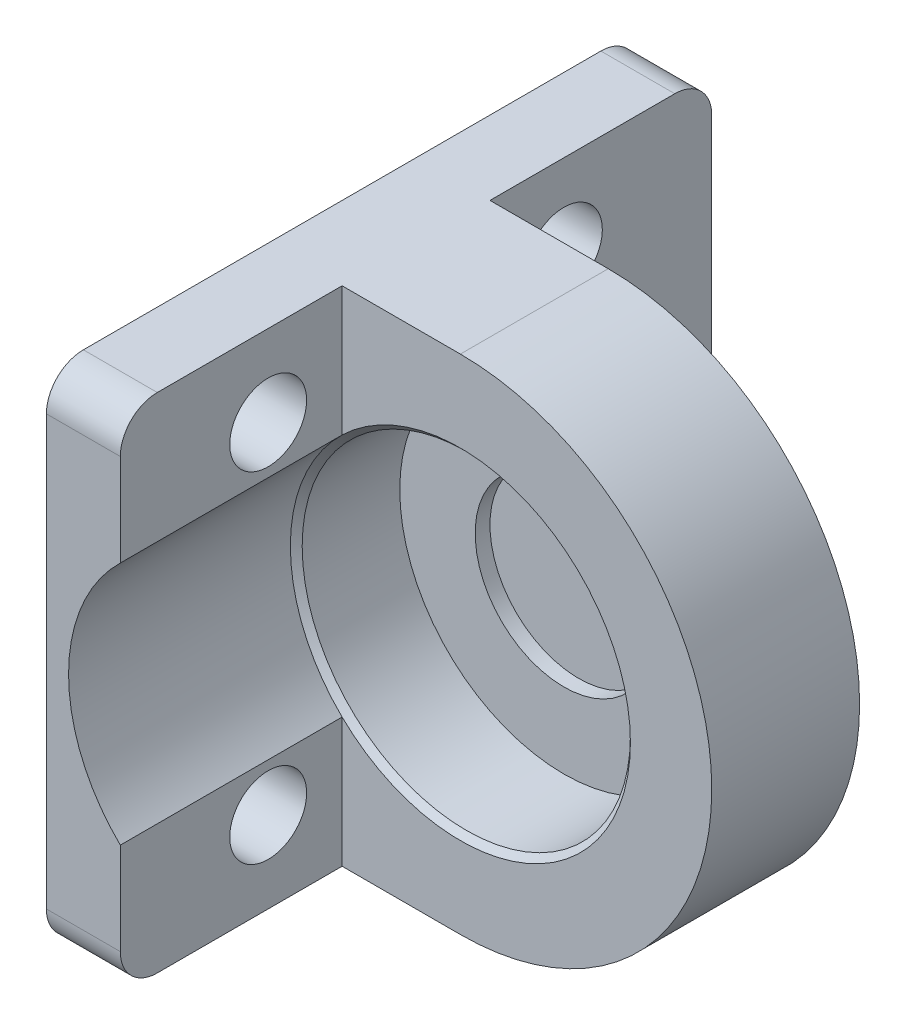
SolidWorks part; units mm, degrees
ref_plane "Спереди" through (0, 0, 0) normal (0, 0, 1) x (1, 0, 0)
ref_plane "Сверху" through (0, 0, 0) normal (0, 1, 0) x (1, 0, 0)
ref_plane "Справа" through (0, 0, 0) normal (1, 0, 0) x (0, 0, -1)
sketch "Эскиз1" plane through (0, 0, 0) normal (0, 0, 1) x (1, 0, 0)
  line L5 (-13, 28.1431) -> (-13, -49971.8569) construction
  line L8 (0, 17) -> (-13, 17)
  line L10 (0, -17) -> (-13, -17)
  line L11 (-13, -17) -> (-13, 17)
  arc A0 (0, -17) -> (0, 17) centre (0, 0) ccw
  dimension "D1" = 17
  dimension "D2" = 13
extrude "Бобышка-Вытянуть1" add sketch "Эскиз1" along normal blind 10
sketch "Эскиз10" plane through (-13, 0, 0) normal (-1, 0, 0) x (0, 0, 1)
  line L0 (25, 19.0139) -> (25, -49980.9861) construction
  line L1 (-15, 32.6282) -> (-15, -49967.3718) construction
  line L2 (10, 17) -> (10, -17) construction
  line L4 (25, 17) -> (-15, 17)
  line L5 (25, 17) -> (25, -17)
  line L6 (25, -17) -> (-15, -17)
  line L7 (-15, 17) -> (-15, -17)
  line L10 (25, 0) -> (-15, 0) construction
  dimension "D1" = 15
  dimension "D2" = 40
  dimension "D5" = 34
  dimension "D6" = 17
extrude "Бобышка-Вытянуть3" add sketch "Эскиз10" against normal blind 5
sketch "Эскиз11" plane through (-8, 0, 0) normal (1, 0, 0) x (0, 0, -1)
  line L0 (15, 17) -> (15, -17) construction
  line L1 (-25, -17) -> (-25, 17) construction
  line L2 (15, -17) -> (-25, -17) construction
  line L4 (-15, -11.5) -> (-15, 11.5) construction
  line L5 (-25, 0) -> (15, 0) construction
  circle A0 centre (5, -11.5) radius 2.6
  circle A1 centre (5, 11.5) radius 2.6
  circle A2 centre (-15, 11.5) radius 2.6
  circle A3 centre (-15, -11.5) radius 2.6
  point P18 (-15, 0)
  dimension "D1" = 5.2
  dimension "D3" = 10
  dimension "D2" = 10
  dimension "D4" = 5.5
extrude "Вырез-Вытянуть7" cut sketch "Эскиз11" against normal through all
sketch "Эскиз2" plane through (0, 0, 10) normal (0, 0, 1) x (1, 0, 0)
  circle A0 centre (0, 0) radius 11.1
  dimension "D1" = 22.2
extrude "Вырез-Вытянуть1" cut sketch "Эскиз2" against normal blind 7
sketch "Эскиз3" plane through (0, 0, 3) normal (0, 0, 1) x (1, 0, 0)
  circle A0 centre (0, 0) radius 6
  dimension "D1" = 12
extrude "Вырез-Вытянуть2" cut sketch "Эскиз3" against normal blind 1
sketch "Эскиз14" plane through (0, 0, 10) normal (0, 0, 1) x (1, 0, 0)
  arc A2 (-8.2883, -7.9721) -> (-8.2883, 7.9721) centre (0, 0) ccw
  circle A3 centre (0, 0) radius 11.5
  dimension "D1" = 0.4
extrude "Вырез-Вытянуть10" cut sketch "Эскиз14" along normal through all
chamfer "Фаска1" distance 0.4 angle 45 1 edges at (11.1, 0, 10)
fillet "Скругление1" radius 2.5 4 edges at (-10.5, -17, -15) (-10.5, 17, -15) (-10.5, 17, 25) (-10.5, -17, 25)
